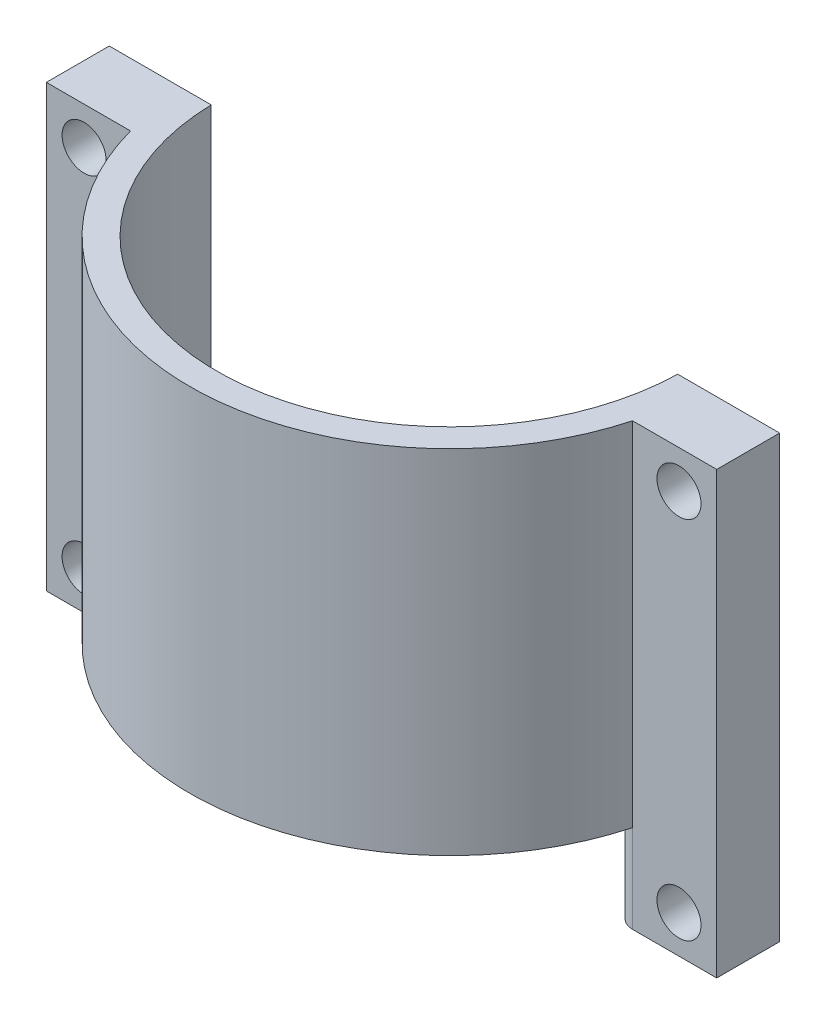
SolidWorks part; units mm, degrees
ref_plane "Front Plane" through (0, 0, 0) normal (0, 0, 1) x (1, 0, 0)
ref_plane "Top Plane" through (0, 0, 0) normal (0, 1, 0) x (1, 0, 0)
ref_plane "Right Plane" through (0, 0, 0) normal (1, 0, 0) x (0, 0, -1)
sketch "Sketch1" plane through (0, 0, 0) normal (0, 0, 1) x (1, 0, 0)
  line L0 (0, 0) -> (0, -2) construction
  line L1 (-3, 3) -> (5.1, 3)
  line L2 (-3, 3) -> (-3, -26)
  line L5 (-3, 3) -> (3, -3) construction
  line L6 (-3, -3) -> (3, 3) construction
  line L7 (50.27, 3) -> (42.17, 3)
  line L8 (50.27, 3) -> (50.27, -26)
  line L11 (50.27, 3) -> (44.27, -3) construction
  line L12 (50.27, -3) -> (44.27, 3) construction
  line L13 (0, -14.5) -> (47.2758, -14.5) construction
  line L14 (50.27, -26) -> (44.27, -32) construction
  line L15 (50.27, -32) -> (44.27, -26) construction
  line L16 (-3, -26) -> (3, -32) construction
  line L17 (-3, -32) -> (3, -26) construction
  line L20 (50.27, -32) -> (50.27, -26)
  line L21 (50.27, -32) -> (42.17, -32)
  line L24 (-3, -32) -> (-3, -26)
  line L25 (-3, -32) -> (5.1, -32)
  line L26 (5.1, 3) -> (5.1, -32)
  line L27 (0, -27) -> (0, -29) construction
  line L28 (42.17, 3) -> (42.17, -32)
  circle A0 centre (0, 0) radius 2 construction
  circle A1 centre (47.27, 0) radius 2 construction
  circle A2 centre (0, 0) radius 1.75
  circle A3 centre (47.27, 0) radius 1.75
  circle A4 centre (47.27, -29) radius 2 construction
  circle A5 centre (0, -29) radius 2 construction
  circle A6 centre (47.27, -29) radius 1.75
  circle A7 centre (0, -29) radius 1.75
  dimension "D1" = 47.27
  dimension "D3" = 4
  dimension "D2" = 6
  dimension "D4" = 6
extrude "Boss-Extrude1" add sketch "Sketch1" along normal blind 5
sketch "Sketch2" plane through (0, 3, 0) normal (0, 1, 0) x (1, 0, 0)
  line L0 (42.17, 0) -> (44.305, 0)
  line L1 (-3, -18) -> (50.27, -18) construction
  line L2 (2.965, 0) -> (5.1, 0)
  arc A0 (5.1, 0) -> (42.17, 0) centre (23.635, 0.4392) ccw
  arc A2 (2.965, 0) -> (44.305, 0) centre (23.635, 0.4392) ccw
  point P14 (23.635, -2.5)
extrude "Boss-Extrude2" add sketch "Sketch1<2>" along normal blind 5
sketch "Sketch1<2>" plane through (0, 0, 0) normal (0, 0, 1) x (1, 0, 0) same geometry as "Sketch1"
extrude "Boss-Extrude3" add sketch "Sketch2" against normal blind 28
fillet "Fillet1" radius 1.4 2 edges at (42.17, -28.5, 5) (5.1, -28.5, 5)
